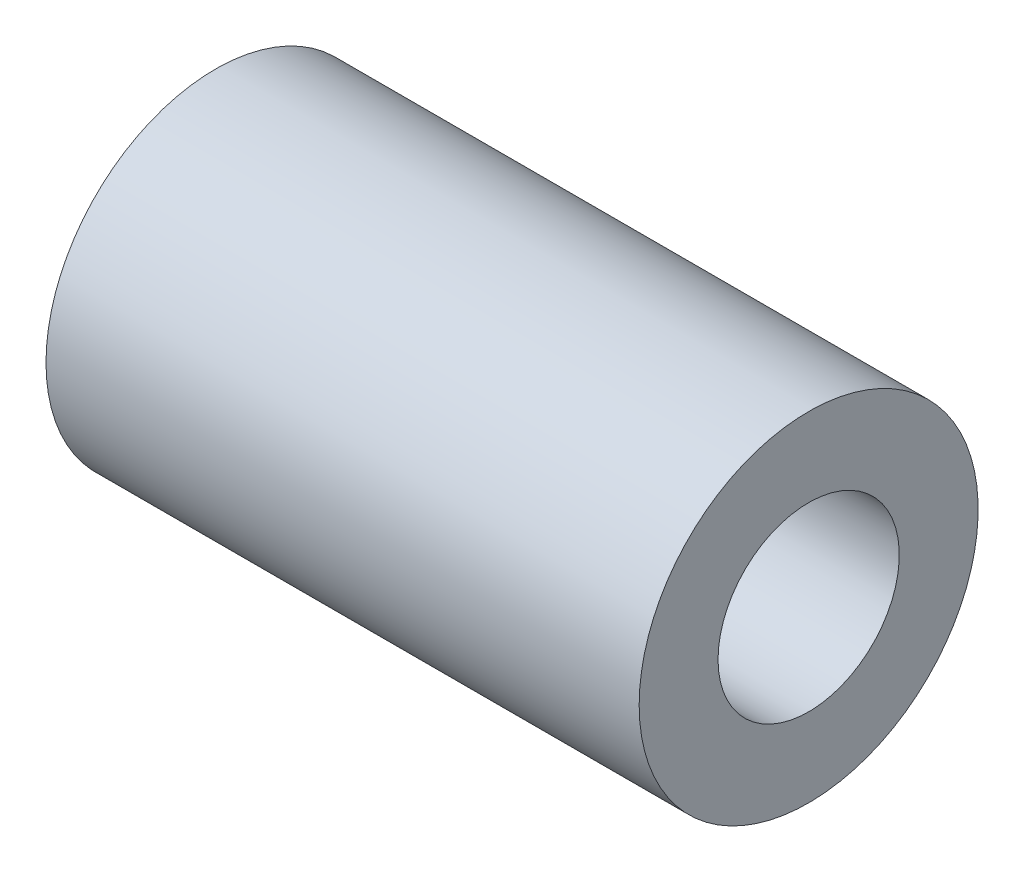
SolidWorks part; units mm, degrees
ref_plane "Front Plane" through (0, 0, 0) normal (0, 0, 1) x (1, 0, 0)
ref_plane "Top Plane" through (0, 0, 0) normal (0, 1, 0) x (1, 0, 0)
ref_plane "Right Plane" through (0, 0, 0) normal (1, 0, 0) x (0, 0, -1)
sketch "Conn_T4_FNPT Sketch" plane through (0, 0, 0) normal (0, 0, 1) x (1, 0, 0)
  line L0 (-1000, 0) -> (1000, 0) construction
  line L1 (0, 0) -> (0, 10.287)
  line L2 (0, 10.287) -> (-36, 10.287)
  line L3 (-36, 10.287) -> (-36, 0)
  line L4 (-36, 0) -> (0, 0)
revolve "Conn_T4_FNPT" add sketch "Conn_T4_FNPT Sketch" angle 360 about L0
ref_axis "Engine Axis" through (1.8, 0, 0) along (-1, 0, 0)
sketch "Socket 1 Sketch" plane through (0, 0, 0) normal (0, 0, 1) x (1, 0, 0)
  line L0 (-1000, 0) -> (1000, 0) construction
  line L1 (1, 0) -> (1, 5.5)
  line L2 (1, 5.5) -> (-14, 5.5)
  line L3 (-14, 5.5) -> (-14, 0)
  line L4 (-14, 0) -> (1, 0)
revolve "Socket 1" cut sketch "Socket 1 Sketch" angle 360 about L0
sketch "Socket 2 Sketch" plane through (0, 0, 0) normal (0, 0, 1) x (1, 0, 0)
  line L0 (-1000, 0) -> (1000, 0) construction
  line L1 (-37, 0) -> (-37, 3.175)
  line L2 (-37, 3.175) -> (-20.8, 3.175)
  line L3 (-20.8, 3.175) -> (-20.8, 0)
  line L4 (-20.8, 0) -> (-37, 0)
revolve "Socket 2" cut sketch "Socket 2 Sketch" angle 360 about L0
